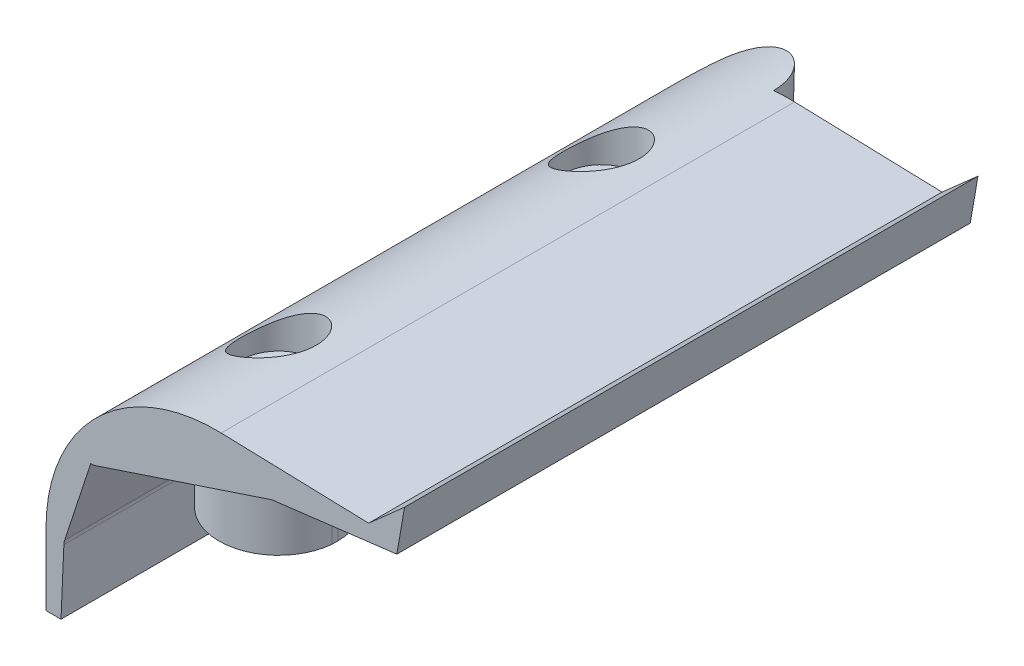
SolidWorks part; units mm, degrees
ref_plane "Front Plane" through (0, 0, 0) normal (0, 0, 1) x (1, 0, 0)
ref_plane "Top Plane" through (0, 0, 0) normal (0, 1, 0) x (1, 0, 0)
ref_plane "Right Plane" through (0, 0, 0) normal (1, 0, 0) x (0, 0, -1)
sketch "Sketch17" plane through (0, 0, 0) normal (0, 0, 1) x (1, 0, 0)
  line L0 (10.5366, 7.9001) -> (10.0814, 5.28)
  line L1 (10.0814, 5.28) -> (2.7434, 4.379)
  line L2 (2.7434, 4.379) -> (-0.7498, 3.218)
  line L3 (-0.7498, 3.218) -> (-0.7498, -3.1433)
  line L4 (-0.7498, -3.1433) -> (-7.7138, -3.1433)
  line L5 (-7.7138, -3.1433) -> (-8.1115, 0.0959)
  line L6 (-8.1115, 0.0959) -> (-9.3366, -4.7001)
  line L7 (-9.3366, -4.7001) -> (-9.3366, -7.9001)
  line L8 (-9.3366, -7.9001) -> (-10.5366, -7.9001)
  line L9 (-10.5366, -7.9001) -> (-10.5366, -3.5001)
  line L10 (-10.5366, -3.5001) -> (-10.5366, 6.5901)
  line L11 (-10.5366, 6.5901) -> (8.4239, 6.0304)
  line L12 (8.4239, 6.0304) -> (10.5366, 7.9001)
extrude "Boss-Extrude1" add sketch "Sketch17" along normal blind 33.7
fillet "Fillet1" radius 20 1 edges at (-9.3366, -4.7001, 16.85)
fillet "Fillet2" radius 10 1 edges at (-10.5366, 6.5901, 16.85)
sketch "Sketch18" plane through (-10.5366, 0, 0) normal (-1, 0, 0) x (0, 0, 1)
  line L0 (33.7, -7.9001) -> (0, -7.9001) construction
  line L1 (22.15, -7.9001) -> (11.45, -7.9001)
  line L2 (22.15, -7.9001) -> (22.15, -3.7095)
  line L3 (22.15, -3.7095) -> (11.45, -3.7095)
  line L4 (11.45, -7.9001) -> (11.45, -3.7095)
  line L5 (33.7, -3.7095) -> (0, -3.7095) construction
  line L6 (0, -3.7095) -> (0, -7.9001) construction
  dimension "D1" = 10.7
  dimension "D2" = 11.45
extrude "Cut-Extrude1" cut sketch "Sketch18" against normal up to surface (1.2118 mm away) up to face at (-9.103, -4.7294, 16.85)
sketch3d "3DSketch4"
  point P0 (2.0898, 6.2174, 12.8945)
ref_plane "Plane4" through (0, 6.2174, 0) normal (0, 1, 0) x (0, 0, 1)
sketch "Sketch32" plane through (0, -3.1433, 0) normal (0, -1, 0) x (1, 0, 0)
  line L0 (-7.7138, 0) -> (-0.7498, 0) construction
  line L1 (-7.7138, 33.7) -> (-7.9127, 33.7)
  line L2 (-0.7318, 26.335) -> (-0.7498, 33.7)
  line L3 (-0.7498, 33.7) -> (-7.7138, 33.7)
  line L4 (-7.7318, 26.3521) -> (-7.7318, 26.335)
  line L6 (-7.7318, 7.365) -> (-7.7318, 7.3479)
  line L7 (-7.7138, 0) -> (-0.7498, 0)
  line L8 (-0.7498, 0) -> (-0.7318, 7.365)
  line L10 (-0.7318, 26.335) -> (-0.7498, 33.7)
  line L11 (-8.1115, 33.7) -> (-7.7138, 33.7) construction
  line L12 (-7.9127, 33.7) -> (-7.9127, 0)
  line L13 (-8.1115, 0) -> (-7.7138, 0) construction
  line L14 (-7.9127, 0) -> (-7.7138, 0)
  line L15 (-7.7318, 26.3521) -> (-7.7318, 7.365)
  arc A0 (-0.7318, 26.335) -> (-7.7318, 26.335) centre (-4.2318, 26.335) ccw
  arc A1 (-7.7318, 7.365) -> (-0.7318, 7.365) centre (-4.2318, 7.365) ccw
  line M11 (-7.7138, 0) -> (-0.7498, 0)
  line M12 (-0.7498, 0) -> (-0.7498, 33.7)
  line M13 (-0.7498, 33.7) -> (-7.7138, 33.7)
  line M14 (-7.7138, 33.7) -> (-7.7138, 0)
  dimension "D2" = 7
  dimension "D1" = 18.97
  dimension "D3" = 7.365
extrude "Cut-Extrude2" cut sketch "Sketch32" against normal up to surface (4.0468 mm away) contours A0 M12 M13 M14 | A1 M14 M11 M12 region at (-4.2318, -3.1433, 31.3354) region at (-4.2318, -3.1433, 2.3646) up to face at (0.9968, 3.7985, 16.85)
sketch "Sketch33" plane through (0, -3.1433, 0) normal (0, -1, 0) x (1, 0, 0)
  line L0 (-0.7498, 26.335) -> (-0.7498, 7.365)
  line L1 (-7.7138, 26.335) -> (-7.7138, 7.365)
  line L2 (-5.0453, 22.9162) -> (-5.0453, 22.9494)
  line L4 (-3.8453, 22.8745) -> (-3.8453, 10.8255)
  line L6 (-5.0453, 22.9162) -> (-5.0453, 10.7506)
  line L7 (-0.7498, 26.6895) -> (-0.7498, 7.0105) construction
  arc A0 (-7.7138, 26.335) -> (-5.0453, 22.9494) centre (-4.2318, 26.335) ccw
  arc A1 (-0.7498, 7.365) -> (-3.8453, 10.8255) centre (-4.2318, 7.365) ccw
  arc A2 (-3.8453, 22.8745) -> (-0.7498, 26.335) centre (-4.2318, 26.335) ccw
  arc A3 (-5.0453, 10.7506) -> (-7.7138, 7.365) centre (-4.2318, 7.365) ccw
  dimension "D1" = 1.2
extrude "Cut-Extrude3" cut sketch "Sketch33" against normal up to surface (5.3325 mm away) up to face at (-3.3585, 2.351, 16.85)
sketch "Sketch35" plane through (-7.7138, 0, 0) normal (1, 0, 0) x (0, 0, -1)
  line L0 (-33.7, 0.9034) -> (-26.6895, 0.9034)
  line L1 (-33.7, 0.9034) -> (-26.6895, 0.9034) construction
  line L2 (-26.6895, 0.9034) -> (-26.5122, -3.1433)
  line L3 (-26.6895, -3.1433) -> (-26.335, -3.1433) construction
  line L4 (-26.5122, -3.1433) -> (-33.7, -3.1433)
  line L5 (-33.7, -3.1433) -> (-26.6895, -3.1433) construction
  line L6 (-33.7, 0.9034) -> (-33.7, -3.1433) construction
  line L7 (-33.7, -3.1433) -> (-33.7, 0.9034)
extrude "Cut-Extrude4" cut sketch "Sketch35" against normal up to surface (1.2252 mm away) up to face at (-8.413, -1.0842, 16.85)
sketch "Sketch36" plane through (-7.7138, 0, 0) normal (1, 0, 0) x (0, 0, -1)
  line L0 (-7.3855, -3.1793) -> (-26.335, -3.1433)
  line L1 (-26.335, -3.1433) -> (-26.335, 0.9034)
  line L2 (-26.335, 0.9034) -> (-7.365, 0.9034) construction
  line L3 (-26.335, 0.9034) -> (-7.365, 0.9034)
  line L4 (-7.365, 0.9034) -> (-7.3855, -3.1793)
extrude "Cut-Extrude5" cut sketch "Sketch36" against normal up to surface (0.1914 mm away) up to face at (-8.4175, -1.1021, 21.7258)
sketch "Sketch37" plane through (-7.7138, 0, 0) normal (1, 0, 0) x (0, 0, -1)
  line L0 (0, 0.9034) -> (0, -3.1433)
  line L1 (0, 0.9034) -> (0, -3.1433) construction
  line L3 (-7.0105, 0.9034) -> (0, 0.9034) construction
  line L4 (-7.0105, 0.9034) -> (-7.0105, -3.1433)
  line L5 (-7.0105, -3.1433) -> (0, -3.1433)
  line L6 (-7.0105, 0.9034) -> (0, 0.9034)
extrude "Cut-Extrude6" cut sketch "Sketch37" against normal up to surface (0.1914 mm away) up to face at (-8.4181, -1.1043, 19.2904)
sketch "Sketch38" plane through (0, 0.0369, 7.3693) normal (0, 0.005, 1) x (1, 0, 0)
  line L0 (-7.7138, 0.8665) -> (-7.9052, 0.8665)
  line L1 (-7.9052, 0.8665) -> (-8.1115, 0.0589)
  line L2 (-8.1115, 0.0589) -> (-7.7138, -3.1803)
  line L3 (-7.7138, -3.1803) -> (-7.7138, 0.8665)
extrude "Cut-Extrude7" cut sketch "Sketch38" against normal through all
sketch "Sketch39" plane through (0, 0, 26.335) normal (0, 0, -1) x (-1, 0, 0)
  line L0 (7.9052, 0.9034) -> (7.7138, 0.9034)
  line L1 (7.9052, 0.9034) -> (7.7138, 0.9034) construction
  line L2 (7.7138, 0.9034) -> (7.7138, -3.1433) construction
  line L3 (7.7138, 0.9034) -> (7.7138, -3.1433)
  line L4 (7.7138, -3.1433) -> (8.1115, 0.0959)
  line L5 (8.1115, 0.0959) -> (7.9052, 0.9034)
extrude "Cut-Extrude8" cut sketch "Sketch39" against normal blind 10
sketch "Sketch40" plane through (0, -3.1433, 0) normal (0, -1, 0) x (1, 0, 0)
  circle A0 centre (-4.2318, 26.335) radius 2.75
  circle A1 centre (-4.2318, 7.365) radius 2.75
  circle A2 centre (-4.2318, 7.365) radius 1.25
  circle A3 centre (-4.2318, 26.335) radius 1.25
  dimension "D1" = 5.5
  dimension "D2" = 2.5
extrude "Cut-Extrude9" cut sketch "Sketch40" against normal through all contours A2 | A3
sketch "Sketch41" plane through (0, -3.1433, 0) normal (0, -1, 0) x (1, 0, 0)
  circle A0 centre (-4.2318, 26.335) radius 2.75
  circle A1 centre (-4.2318, 7.365) radius 2.75
  dimension "D1" = 5.5
extrude "Cut-Extrude10" cut sketch "Sketch41" against normal blind 5 contours A1 | A0
sketch "Sketch42" plane through (0, 6.2174, 0) normal (0, 1, 0) x (0, 0, 1)
  circle A0 centre (7.365, -4.2318) radius 2.2083
  circle A1 centre (26.335, -4.2318) radius 2.2083
  dimension "D1" = 4.4166
extrude "Cut-Extrude11" cut sketch "Sketch42" against normal blind 3
sketch "Sketch43" plane through (0, 0, 33.7) normal (0, 0, 1) x (1, 0, 0)
  line L0 (-7.9052, 0.9034) -> (-8.8229, -1.8871)
  line L1 (-8.8229, -1.8871) -> (-9.4804, -3.8866)
  line L2 (-9.4804, -3.8866) -> (-9.6549, -7.9001)
  line L3 (-10.5366, -7.9001) -> (-9.3366, -7.9001) construction
  line L4 (-9.6549, -7.9001) -> (-8.3641, -7.9001)
  line L5 (-8.3641, -7.9001) -> (-7.9052, 0.9034)
extrude "Cut-Extrude12" cut sketch "Sketch43" against normal through all
fillet "Fillet3" radius 1 2 edges at (-9.4804, -3.8866, 5.725) (-9.4804, -3.8866, 27.925)
sketch "Sketch44" plane through (0.1852, 6.2736, 0) normal (0.0295, 0.9996, 0) x (0.9996, -0.0295, 0)
  line L1 (9.4063, 0) -> (-4.6417, 0)
  circle A0 centre (-4.6417, 0) radius 2.9803
extrude "Boss-Extrude2" add sketch "Sketch44" against normal up to surface (5.5588 mm away) contours A0 up to face at (-2.8947, 2.5051, 16.85)
sketch "Sketch46" plane through (0.1852, 6.2736, 0) normal (0.0295, 0.9996, 0) x (0.9996, -0.0295, 0)
  circle A0 centre (-4.6417, 0) radius 2.9803
extrude "Cut-Extrude13" cut sketch "Sketch46" against normal up to surface (3.0551 mm away) up to face at (-6.7805, 1.3306, 12.9967)
sketch "Sketch47" plane through (0, 6.2174, 0) normal (0, 1, 0) x (0, 0, 1)
  line L0 (-2.2741, -6.4421) -> (-1.429, -8.0028)
  line L1 (-1.429, -8.0028) -> (0, -7.5236)
  spline S0 degree 2 poles (0, -7.5236) (-1.3341, -7.2798) (-2.2741, -6.4421) knots 0 0 0 1 1 1
  spline S1 degree 3 poles (0, -7.5236) (-0.2111, -7.5236) (-0.4159, -7.5008) (-0.8146, -7.4142) (-1.0076, -7.3499) (-1.3642, -7.1909) (-1.5322, -7.0944) (-1.8384, -6.879) (-1.9777, -6.7599) (-2.2325, -6.4996) (-2.3485, -6.3574) (-2.5514, -6.0583) (-2.6392, -5.9008) (-2.7873, -5.5687) (-2.8478, -5.3929) (-2.9357, -5.0347) (-2.9638, -4.8512) (-2.9861, -4.475) (-2.9798, -4.2797) (-2.9294, -3.8935) (-2.8858, -3.7026) (-2.7596, -3.3265) (-2.6754, -3.1389) (-2.4712, -2.7867) (-2.3517, -2.6214) (-2.0766, -2.3141) (-1.9205, -2.1726) (-1.5866, -1.9285) (-1.4061, -1.8232) (-1.0234, -1.6517) (-0.826, -1.5873) (-0.4192, -1.5001) (-0.208, -1.4777) (0, -1.4777) knots 0 0 0 0 0.0625 0.0625 0.125 0.125 0.1875 0.1875 0.25 0.25 0.3125 0.3125 0.375 0.375 0.4375 0.4375 0.5 0.5 0.5625 0.5625 0.625 0.625 0.6875 0.6875 0.75 0.75 0.8125 0.8125 0.875 0.875 0.9375 0.9375 1 1 1 1 construction
extrude "Cut-Extrude14" cut sketch "Sketch47" against normal up to surface (5.41 mm away) up to face at (-3.1364, 2.4248, 14.23)
